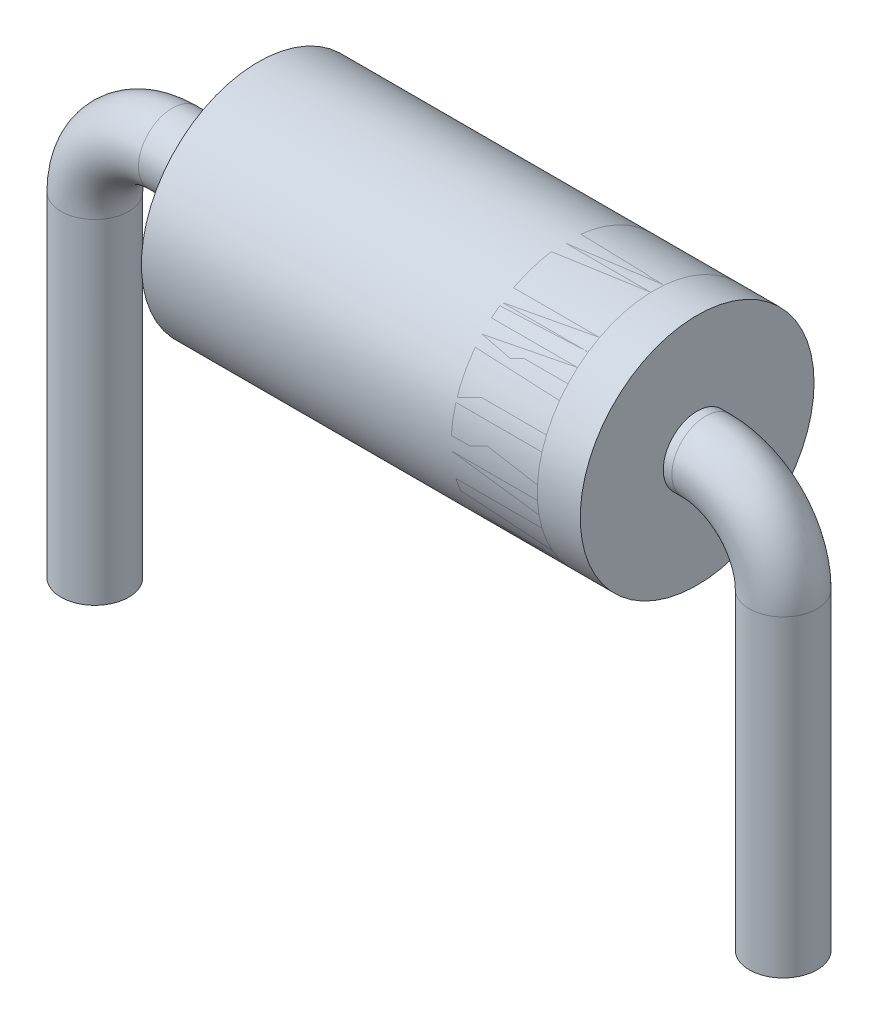
SolidWorks part; units mm, degrees
ref_plane "Alzado" through (0, 0, 0) normal (0, 0, 1) x (1, 0, 0)
ref_plane "Planta" through (0, 0, 0) normal (0, 1, 0) x (1, 0, 0)
ref_plane "Vista lateral" through (0, 0, 0) normal (1, 0, 0) x (0, 0, -1)
sketch "Croquis2" plane through (0, 0, 0) normal (1, 0, 0) x (0, 0, -1)
  circle A0 centre (0, 0) radius 1.3589
  dimension "D1" = 2.7178
extrude "Saliente-Extruir1" add sketch "Croquis2" along normal blind 0.5 and the other way blind 0.5
sketch "Croquis3" plane through (0, 0, 0) normal (1, 0, 0) x (0, 0, -1)
  circle A0 centre (0, 0) radius 1.3589
extrude "Saliente-Extruir2" add sketch "Croquis3" along normal blind 0.5 from offset 0.5 separate body
sketch "Croquis4" plane through (0, 0, 0) normal (1, 0, 0) x (0, 0, -1)
  circle A0 centre (0, 0) radius 1.3589
extrude "Saliente-Extruir3" add sketch "Croquis4" against normal blind 4.6 from offset 0.5 separate body
sketch "Croquis5" plane through (0, 0, 0) normal (1, 0, 0) x (0, 0, -1)
  circle A0 centre (0, 0) radius 0.3937
  dimension "D1" = 0.7874
sketch "Croquis7" plane through (0, 0, 0) normal (0, 0, 1) x (1, 0, 0)
  line L0 (-1.1, 0) -> (1.1, 0)
  line L1 (1.4948, 0) -> (-1.4948, 0) construction
  line L2 (2, -0.9) -> (2, -4.5341)
  line L3 (0, 0) -> (0, -3.4645) construction
  line L4 (0, -1.4948) -> (0, 1.4948) construction
  line L5 (-2, -0.9) -> (-2, -4.5341)
  arc A0 (1.1, 0) -> (2, -0.9) centre (1.1, -0.9) cw
  arc A1 (-1.1, 0) -> (-2, -0.9) centre (-1.1, -0.9) ccw
  point P8 (2, 0)
  point P16 (-2, 0)
  dimension "D3" = 0.9
  dimension "D1" = 2
  dimension "D2" = 4.5341
sweep "Barrer1" add profiles "Croquis5" path "Croquis7"
sketch "Croquis8" plane through (0, 0, 0) normal (1, 0, 0) x (0, 0, -1)
  circle A0 centre (0, 0) radius 0.3937
sketch "Croquis9" plane through (0, 0, 0) normal (0, 0, 1) x (1, 0, 0)
  line L0 (0, 0) -> (-5.1, 0)
  line L1 (1.4948, 0) -> (-1.4948, 0) construction
  line L2 (-6, -0.9) -> (-6, -4.7835)
  arc A0 (-6, -0.9) -> (-5.1, 0) centre (-5.1, -0.9) cw
  point P8 (-6, 0)
  dimension "D3" = 0.9
  dimension "D1" = 6
  dimension "D2" = 4.7835
sweep "Barrer2" add profiles "Croquis8" path "Croquis9"
